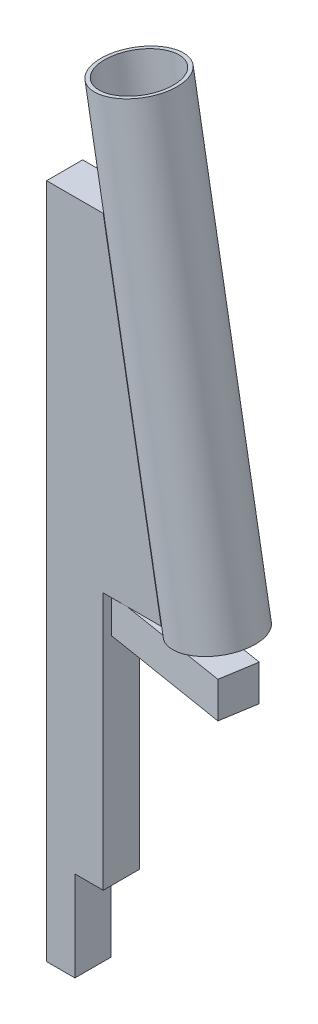
SolidWorks part; units mm, degrees
ref_plane "Front Plane" through (0, 0, 0) normal (0, 0, 1) x (1, 0, 0)
ref_plane "Top Plane" through (0, 0, 0) normal (0, 1, 0) x (1, 0, 0)
ref_plane "Right Plane" through (0, 0, 0) normal (1, 0, 0) x (0, 0, -1)
sketch "Esquisse1" plane through (0, 0, 0) normal (0, 0, 1) x (1, 0, 0)
  line L0 (0, 525.2077) -> (0, 0)
  line L1 (0, 0) -> (22, 0)
  line L2 (22, 0) -> (22, 70)
  line L3 (22, 70) -> (44, 70)
  line L4 (44, 70) -> (44, 270)
  line L5 (44, 270) -> (89, 270)
  line L6 (89, 270) -> (44, 525.2077)
  line L7 (44, 525.2077) -> (0, 525.2077)
  dimension "D1" = 100
  dimension "D2" = 22
  dimension "D3" = 45
  dimension "D4" = 70
  dimension "D5" = 22
  dimension "D6" = 270
extrude "Main Extrusion" add sketch "Esquisse1" along normal mid plane 28
sketch "Esquisse2" plane through (0, 270, 0) normal (0, -1, 0) x (-1, 0, 0)
  line L0 (-61.7505, -13.8181) -> (-66.2495, 13.8181) construction
  line L1 (-47.9324, -11.5686) -> (-146.6332, -27.6362)
  line L2 (-47.9324, -11.5686) -> (-52.4314, 16.0676)
  line L3 (-52.4314, 16.0676) -> (-151.1321, 0)
  line L4 (-146.6332, -27.6362) -> (-151.1321, 0)
  line L5 (-148.8826, -13.8181) -> (-50.1819, 2.2495) construction
  line L9 (-44, -14) -> (-44, 14) construction
  point P8 (-64, 0)
  point P11 (-44, 0)
  point P12 (-131.9243, -52.7474)
  point P13 (-150, 14)
  point P14 (-151.1321, 0)
  dimension "D1" = 28
  dimension "D2" = 100
  dimension "D3" = 86
  dimension "D4" = 20
extrude "Lock Extrusion" add sketch "Esquisse2" along normal blind 28
ref_plane "Plan3" through (-43.489, 246.6386, 0) normal (0.1736, -0.9848, 0) x (0, 0, -1)
sketch "Esquisse3" plane through (-43.489, 246.6386, 0) normal (0.1736, -0.9848, 0) x (0, 0, -1)
  line L2 (-14, 134.5329) -> (14, 134.5329) construction
  line L3 (0, 48.95) -> (0, -48.95) construction
  circle A0 centre (0, 164.5329) radius 27
  circle A1 centre (0, 164.5329) radius 30
  dimension "D1" = 60
  dimension "D2" = 54
extrude "Plexiglas" add sketch "Esquisse3" against normal blind 350 separate body
